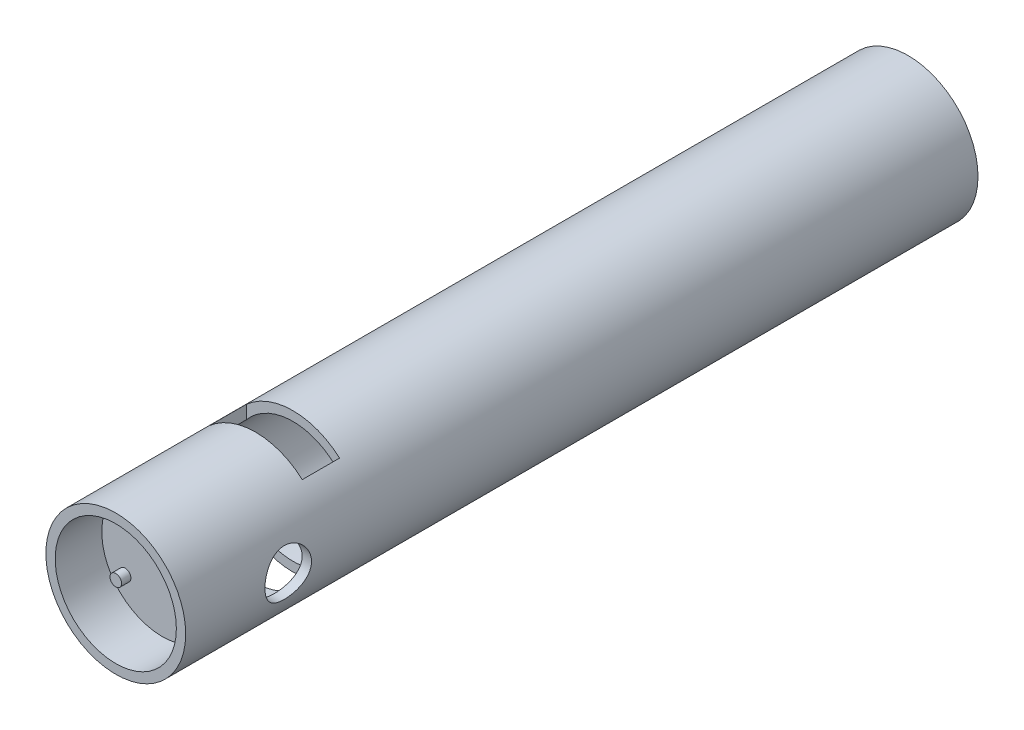
SolidWorks part; units mm, degrees
ref_plane "Plano frontal" through (0, 0, 0) normal (0, 0, 1) x (1, 0, 0)
ref_plane "Plano superior" through (0, 0, 0) normal (0, 1, 0) x (1, 0, 0)
ref_plane "Plano direito" through (0, 0, 0) normal (1, 0, 0) x (0, 0, -1)
sketch "Esboço1" plane through (0, 0, 0) normal (1, 0, 0) x (0, 0, -1)
  line L0 (-60, 0) -> (60, 0)
  line L4 (-60, 0) -> (-60, 15)
  line L5 (-60, 15) -> (60, 15)
  line L7 (60, 0) -> (110, 0)
  line L9 (110, 15) -> (60, 15)
  line L10 (110, 15) -> (110, 0)
  point P4 (0, 0)
  dimension "D1" = 170
  dimension "D3" = 15
revolve "Revolução1" add sketch "Esboço1" angle 360 about L0
sketch "Esboço2" plane through (0, 0, 60) normal (0, 0, 1) x (1, 0, 0)
  circle A0 centre (0, 0) radius 13
  dimension "D1" = 26
extrude "Corte-extrusão1" cut sketch "Esboço2" against normal through all
ref_plane "Plano1" through (0, 0, 50) normal (0, 0, 1) x (1, 0, 0)
sketch "Esboço3" plane through (0, 0, 50) normal (0, 0, 1) x (1, 0, 0)
  circle A0 centre (0, 0) radius 13
  point P0 (0, 0)
  dimension "D1" = 26
extrude "Ressalto-extrusão1" add sketch "Esboço3" against normal blind 5 separate body
sketch "Esboço4" plane through (0, 0, 50) normal (0, 0, 1) x (1, 0, 0)
  line L1 (10, -7.5) -> (-10, -7.5) construction
  line L2 (10, -7.5) -> (10, 7.5) construction
  line L3 (10, 7.5) -> (-10, 7.5) construction
  line L4 (-10, -7.5) -> (-10, 7.5) construction
  line L5 (10, -7.5) -> (-10, 7.5) construction
  line L6 (10, 7.5) -> (-10, -7.5) construction
  circle A0 centre (-8, -5.5) radius 1.25
  circle A1 centre (8, -5.5) radius 1.25
  point P0 (0, 0)
  dimension "D5" = 2.5
  dimension "D6" = 2
  dimension "D1" = 20
  dimension "D2" = 15
  dimension "D3" = 2
  dimension "D4" = 2
extrude "Ressalto-extrusão2" add sketch "Esboço4" along normal blind 2
sketch "Esboço5" plane through (0, 0, 50) normal (0, 0, 1) x (1, 0, 0)
  line L0 (-10, 4.5) -> (10, 4.5)
  line L2 (10, 4.5) -> (10, 7.5)
  line L3 (10, 7.5) -> (-10, 7.5)
  line L4 (-10, 4.5) -> (-10, 7.5)
  point P0 (0, 0)
  dimension "D1" = 20
  dimension "D2" = 4.5
  dimension "D3" = 3
  dimension "D4" = 10
extrude "Corte-extrusão2" cut sketch "Esboço5" against normal up to next
sketch "Esboço6" plane through (0, 0, 0) normal (1, 0, 0) x (0, 0, -1)
  line L0 (0, 0) -> (-60, 0) construction
  line L1 (-60, 15) -> (-60, -15) construction
  circle A0 centre (-38, 0) radius 5
  dimension "D2" = 10
  dimension "D1" = 22
extrude "Corte-extrusão3" cut sketch "Esboço6" against normal through all both and the other way through all
sketch "Esboço7" plane through (0, 0, 0) normal (0, 1, 0) x (1, 0, 0)
  line L0 (0, -38) -> (0, -45) construction
  line L1 (0, 0) -> (0, -60) construction
  line L2 (0, -38) -> (0, -21.9845) construction
  line L4 (0, -21.9845) -> (10, -21.9845)
  line L5 (0, -21.9845) -> (-10, -21.9845)
  line L6 (-10, -21.9845) -> (-10, -29.9845)
  line L7 (-10, -29.9845) -> (10, -29.9845)
  line L8 (10, -29.9845) -> (10, -21.9845)
  point P10 (0, -21.9845)
  dimension "D1" = 20
  dimension "D2" = 8
extrude "Corte-extrusão4" cut sketch "Esboço7" against normal through all both and the other way through all
